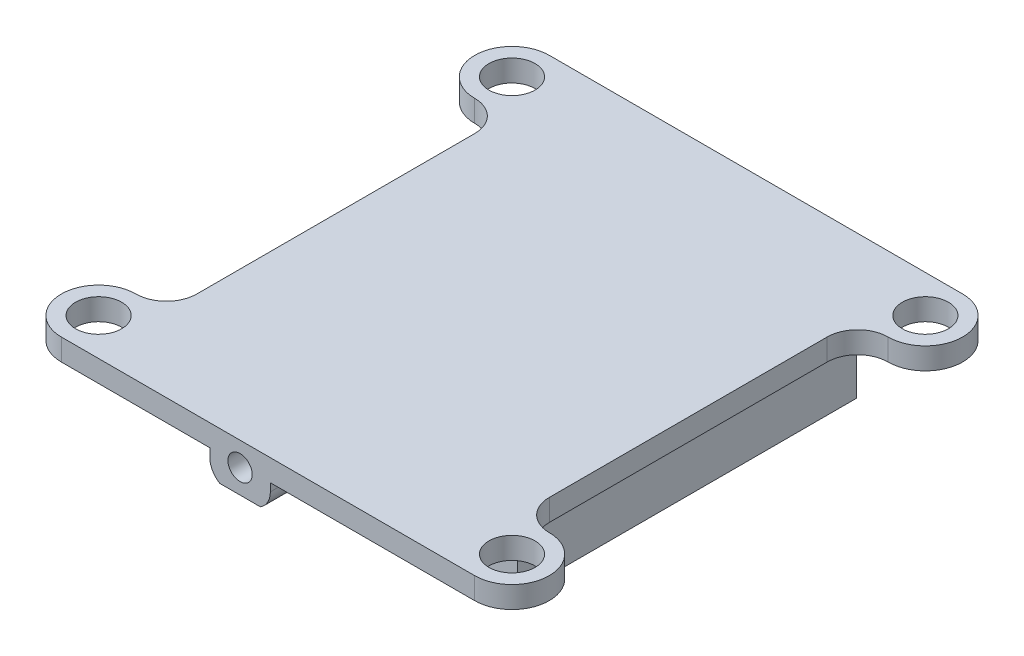
SolidWorks part; units mm, degrees
ref_plane "Front Plane" through (0, 0, 0) normal (0, 0, 1) x (1, 0, 0)
ref_plane "Top Plane" through (0, 0, 0) normal (0, 1, 0) x (1, 0, 0)
ref_plane "Right Plane" through (0, 0, 0) normal (1, 0, 0) x (0, 0, -1)
sketch "Sketch1" plane through (0, 0, 0) normal (0, 1, 0) x (1, 0, 0)
  line L0 (0, 14.2402) -> (0, -22.8173) construction
  line L1 (-20.2546, 0) -> (19.294, 0) construction
  line L2 (-13, -10.25) -> (-13, 10.25)
  line L11 (-15.25, -18) -> (15.25, -18)
  line L13 (-15.25, 18) -> (15.25, 18)
  line L15 (-15.25, -15.25) -> (15.25, 15.25) construction
  line L16 (-15.25, 15.25) -> (15.25, -15.25) construction
  line L17 (13, -10.25) -> (13, 10.25)
  line L19 (-12.9, 12.5) -> (12.9, 12.5)
  line L20 (-12.9, 12.5) -> (-12.9, -12.5)
  line L21 (-12.9, -12.5) -> (12.9, -12.5)
  line L22 (12.9, 12.5) -> (12.9, -12.5)
  line L23 (-12.9, 12.5) -> (12.9, -12.5) construction
  line L24 (-12.9, -12.5) -> (12.9, 12.5) construction
  circle A0 centre (-15.25, 15.25) radius 1.7
  circle A1 centre (15.25, 15.25) radius 1.7
  circle A2 centre (15.25, -15.25) radius 1.7
  circle A3 centre (-15.25, -15.25) radius 1.7
  circle A4 centre (-15.25, 15.25) radius 2.75
  circle A5 centre (15.25, 15.25) radius 2.75
  circle A6 centre (-15.25, -15.25) radius 2.75
  circle A7 centre (15.25, -15.25) radius 2.75
  arc A8 (-13, 10.25) -> (-15.25, 12.5) centre (-15.25, 10.25) ccw
  arc A9 (13, 10.25) -> (15.25, 12.5) centre (15.25, 10.25) cw
  arc A10 (13, -10.25) -> (15.25, -12.5) centre (15.25, -10.25) ccw
  arc A11 (-13, -10.25) -> (-15.25, -12.5) centre (-15.25, -10.25) cw
  point P7 (0, 0)
  point P8 (0, 0)
  point P36 (13, 0)
  point P37 (-13, 0)
  point P39 (0, 0)
  dimension "D1" = 3.4
  dimension "D3" = 26
  dimension "D2" = 30.5
  dimension "D4" = 36
  dimension "D5" = 30.5
  dimension "D7" = 0.1
extrude "Boss-Extrude1" add sketch "Sketch1" along normal blind 1.6 contours L2 A11 A6 L11 A7 A10 L17 A9 A5 L13 A4 A8 | A5 A1 | A4 A0 | A6 A3 | A7 A2 | L20 L19 L22 L21 region at (-12.9528, 0, 0) region at (-13.3605, 0, 13.3605) region at (-17.9222, 0, -15.25) region at (12.5778, 0, 15.25) region at (17.1395, 0, -17.1395)
extrude "Boss-Extrude2" add sketch "Sketch1<3>" against normal blind 3.5 contours L22 L19 L20 L21 region at (0, 0, 0)
sketch "Sketch1<3>" plane through (0, 0, 0) normal (0, 1, 0) x (1, 0, 0) same geometry as "Sketch1"
sketch "Sketch2" plane through (0, 0, 18) normal (0, 0, 1) x (1, 0, 0)
  line L0 (-2.065, 8.1739) -> (-2.065, -13.1813) construction
  line L2 (-12.9, 0) -> (12.9, 0) construction
  line L3 (-12.9, 0) -> (12.9, 0) construction
  line L4 (-4.3, 0) -> (-3.765, 0)
  line L5 (-4.3, 0) -> (-4.3, -0.5859)
  line L6 (-3.5628, -1.91) -> (-0.5672, -1.91)
  line L7 (0.17, 0) -> (0.17, -0.5859)
  line L8 (0.17, 0) -> (-0.365, 0)
  line L9 (-3.765, 0) -> (-3.765, 1.6)
  line L10 (-3.765, 1.6) -> (-0.365, 1.6)
  line L11 (-15.25, 1.6) -> (15.25, 1.6) construction
  line L12 (-0.365, 0) -> (-0.365, 1.6)
  line L13 (-12.9, -3.5) -> (-12.9, 0) construction
  arc A0 (-4.3, -0.5859) -> (-3.5628, -1.91) centre (-2.7423, -0.5859) ccw
  circle A1 centre (-2.065, -0.15) radius 0.8958
  arc A2 (0.17, -0.5859) -> (-0.5672, -1.91) centre (-1.3877, -0.5859) cw
  point P4 (-4.3, -0.5859)
  point P7 (-2.065, 0)
  point P20 (-3.765, 0.8)
  point P26 (-2.065, -1.91)
  point P31 (-2.065, 1.6)
  line M16 (-15.25, 0) -> (15.25, 0)
  dimension "D1" = 8.6
  dimension "D2" = 3.51
  dimension "D3" = 3.4
  dimension "D4" = 4.47
  dimension "D5" = 1.75
  dimension "D6" = 0.15
extrude "Boss-Extrude3" add sketch "Sketch2" against normal up to surface (5.5 mm away) up to face at (0, -1.75, 12.5)
extrude "Cut-Extrude1" cut sketch "Sketch2<2>" against normal up to surface (5.5 mm away) contours A1 M16 | A1 M16 region at (-2.065, -0.4505, 18) region at (-2.065, 0.3125, 18) up to face at (-1.239, -1.2183, 12.5)
sketch "Sketch2<2>" plane through (0, 0, 18) normal (0, 0, 1) x (1, 0, 0) same geometry as "Sketch2"
